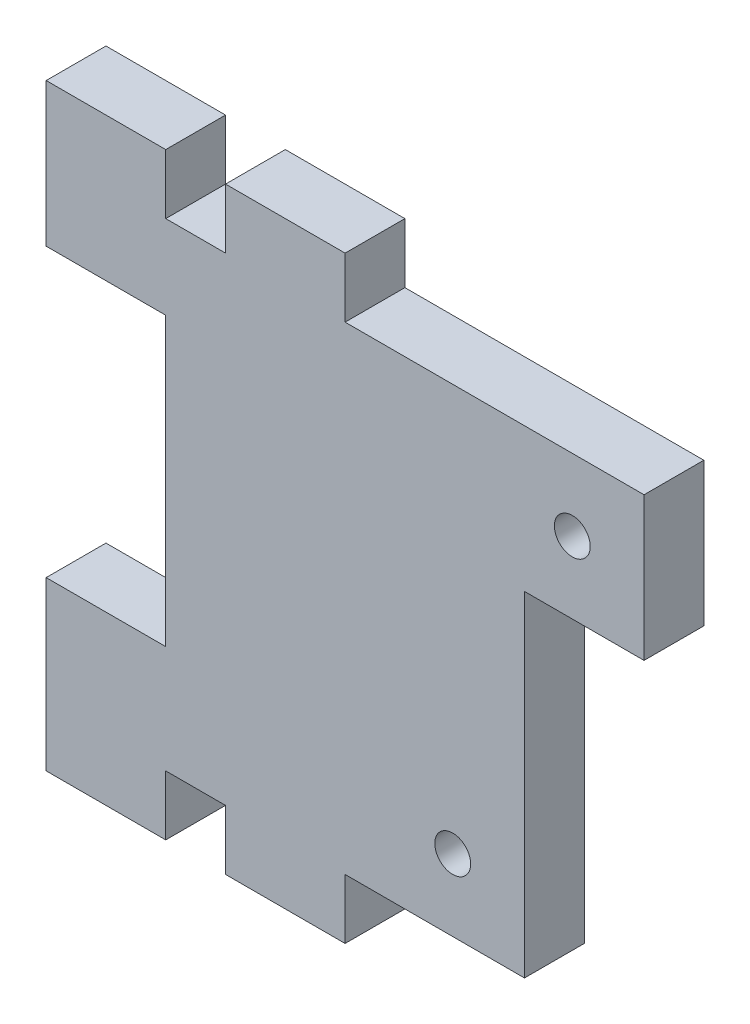
SolidWorks part; units mm, degrees
ref_plane "Plan de face" through (0, 0, 0) normal (0, 0, 1) x (1, 0, 0)
ref_plane "Plan de dessus" through (0, 0, 0) normal (0, 1, 0) x (1, 0, 0)
ref_plane "Plan de droite" through (0, 0, 0) normal (1, 0, 0) x (0, 0, -1)
sketch "Esquisse1" plane through (0, 0, 0) normal (0, 0, 1) x (1, 0, 0)
  line L0 (0, 20) -> (40, 20) construction
  line L1 (10, 0) -> (15, 0)
  line L2 (0, 0) -> (0, 9)
  line L3 (10, 40) -> (15, 40)
  line L4 (50, 28) -> (50, 40)
  line L5 (25, 40) -> (50, 40)
  line L6 (0, 40) -> (0, 45)
  line L7 (0, 45) -> (10, 45)
  line L8 (10, 40) -> (10, 45)
  line L9 (25, 0) -> (40, 0)
  line L10 (15, 40) -> (15, 45)
  line L11 (15, 45) -> (25, 45)
  line L12 (25, 40) -> (25, 45)
  line L13 (25, 0) -> (25, -5)
  line L14 (15, -5) -> (25, -5)
  line L15 (15, 0) -> (15, -5)
  line L16 (10, 0) -> (10, -5)
  line L17 (0, -5) -> (10, -5)
  line L18 (0, 0) -> (0, -5)
  line L19 (0, 33) -> (0, 40)
  line L20 (0, 9) -> (10, 9)
  line L22 (0, 33) -> (10, 33)
  line L23 (10, 9) -> (10, 33)
  line L25 (40, 0) -> (40, 28)
  line L26 (40, 28) -> (50, 28)
  circle A0 centre (44, 34) radius 1.5
  circle A1 centre (34, 6) radius 1.5
  dimension "D9" = 3
  dimension "D11" = 6
  dimension "D1" = 40
  dimension "D2" = 50
  dimension "D3" = 10
  dimension "D4" = 5
  dimension "D5" = 5
  dimension "D6" = 10
  dimension "D7" = 9
  dimension "D8" = 24
  dimension "D10" = 6
  dimension "D12" = 6
  dimension "D13" = 16
  dimension "D14" = 10
  dimension "D15" = 28
extrude "Boss.-Extru.1" add sketch "Esquisse1" along normal blind 5
